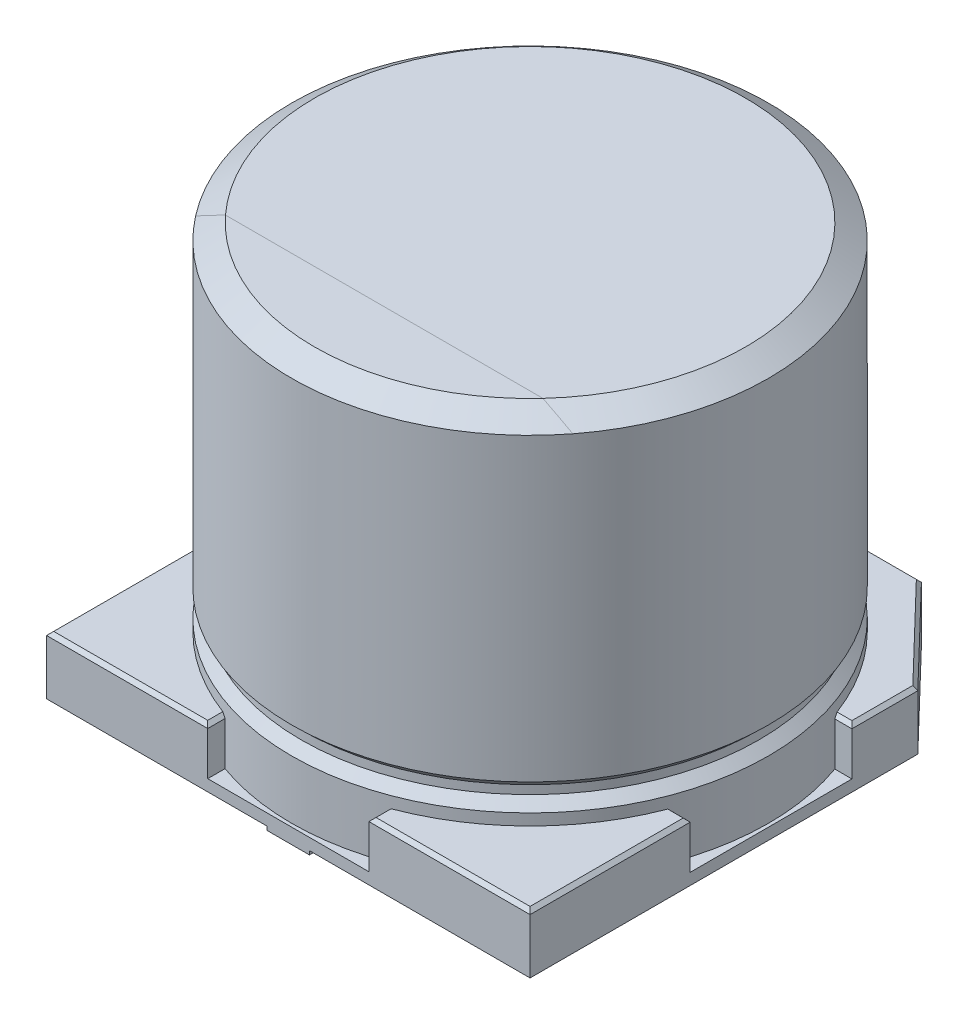
SolidWorks part; units mm, degrees
ref_plane "Front Plane" through (0, 0, 0) normal (0, 0, 1) x (1, 0, 0)
ref_plane "Top Plane" through (0, 0, 0) normal (0, 1, 0) x (1, 0, 0)
ref_plane "Right Plane" through (0, 0, 0) normal (1, 0, 0) x (0, 0, -1)
sketch "Sketch1" plane through (0, 0, 0) normal (0, 1, 0) x (1, 0, 0)
  line L0 (0, 3.315) -> (0, -3.315) construction
  point P2 (0, 0)
  line B0 (3.315, -3.315) -> (3.315, 2.0024)
  line B1 (0.2896, -3.315) -> (3.315, -3.315)
  line B2 (2.0517, 3.315) -> (3.315, 2.0024)
  line B3 (2.0517, 3.315) -> (0.2875, 3.315)
  line B4 (0.2882, 1.5924) -> (0.2875, 3.315)
  line B5 (0.2875, 3.315) -> (-0.2875, 3.315)
  line B6 (-0.2875, 3.315) -> (-0.2882, 1.5924)
  line B7 (-0.2875, 3.315) -> (-2.0519, 3.315)
  line B8 (-0.2882, 1.5924) -> (0.2882, 1.5924)
  line B9 (0.2889, -1.5924) -> (-0.2889, -1.5924)
  line B10 (0.2896, -3.315) -> (0.2889, -1.5924)
  line B11 (-0.2889, -1.5924) -> (-0.2896, -3.315)
  line B12 (-0.2896, -3.315) -> (0.2896, -3.315)
  line B13 (-3.315, -3.315) -> (-0.2896, -3.315)
  line B14 (-3.315, 2.0024) -> (-3.315, -3.315)
  line B15 (-3.315, 2.0024) -> (-2.0519, 3.315)
  line B16 (-3.315, -1.1187) -> (-1.11, -1.105)
  line B17 (-1.11, -1.105) -> (-1.105, -3.315)
  line B18 (-1.115, 1.105) -> (-3.315, 1.0983)
  line B19 (-1.12, 3.315) -> (-1.115, 1.105)
  line B20 (1.11, -1.105) -> (3.315, -1.1187)
  line B21 (1.105, -3.315) -> (1.11, -1.105)
  line B22 (1.115, 1.105) -> (1.12, 3.315)
  line B23 (3.315, 1.0983) -> (1.115, 1.105)
sketch_block_instance "Block1-1"
sketch_block "Block1"
extrude "Boss-Extrude1" add sketch "Sketch1" against normal blind 0.1571 contours B19 B7 B15 B14 B18 | L0 B8 B6 B7 B19 B18 B14 B16 B17 B13 B11 B9 | B17 B16 B14 B13 | B9 L0 B12 B10 | L0 B9 B11 B12 | L0 B5 B6 B8 | B5 L0 B8 B4 | B8 L0 B9 B10 B1 B21 B20 B0 B23 B22 B3 B4 | B23 B0 B2 B3 B22 | B21 B1 B0 B20 region at (0.1439, 0, -2.4533) region at (-0.1439, 0, -2.4533) region at (1.3107, 0, -0.0031) region at (-1.3107, 0, -0.0031) region at (0.1446, 0, 2.454) region at (-0.1446, 0, 2.454) region at (2.0777, 0, -2.0703) region at (-2.0777, 0, -2.0704) region at (-2.2101, 0, 2.2138) region at (2.2101, 0, 2.2138)
extrude "Boss-Extrude2" add sketch "Sketch1<4>" along normal blind 0.6443 contours B19 B7 B15 B14 B18 | B17 B16 B14 B13 | B23 B0 B2 B3 B22 | B21 B1 B0 B20 region at (2.2101, 0, 2.2138) region at (2.0777, 0, -2.0703) region at (-2.2101, 0, 2.2138) region at (-2.0777, 0, -2.0704)
sketch "Sketch1<4>" plane through (0, 0, 0) normal (0, 1, 0) x (1, 0, 0) same geometry as "Sketch1"
chamfer "Chamfer1" distance 0.0487 angle 45 18 edges at (2.2125, 0.6443, 1.1119) (3.315, 0.6443, 2.2169) (2.21, 0.6443, 3.315) (1.1075, 0.6443, 2.21) (1.1175, 0.6443, -2.21) (1.5858, 0.6443, -3.315) (2.6833, 0.6443, -2.6587) (3.315, 0.6443, -1.5504) (2.215, 0.6443, -1.1017) (-2.215, 0.6443, -1.1017) (-3.315, 0.6443, -1.5504) (-2.6835, 0.6443, -2.6587) (-1.586, 0.6443, -3.315) (-1.1175, 0.6443, -2.21) (-2.21, 0.6443, 3.315) (-3.315, 0.6443, 2.2169) (-2.2125, 0.6443, 1.1119) (-1.1075, 0.6443, 2.21)
extrude "Boss-Extrude3" add sketch "Sketch1<5>" against normal blind 0.0514 from surface contours L0 B9 B11 B12 | B9 L0 B12 B10 | L0 B5 B6 B8 | B5 L0 B8 B4 region at (0.1439, 0, -2.4533) region at (-0.1439, 0, -2.4533) region at (0.1446, 0, 2.454) region at (-0.1446, 0, 2.454) starting at face at (0, -0.1571, -0.6675)
sketch "Sketch1<5>" plane through (0, 0, 0) normal (0, 1, 0) x (1, 0, 0) same geometry as "Sketch1"
sketch "Sketch2" plane through (0, 0, 0) normal (0, 1, 0) x (1, 0, 0)
  circle A0 centre (0, 0) radius 3.27
  dimension "D1" = 6.54
extrude "Boss-Extrude4" add sketch "Sketch2" along normal blind 5.5
chamfer "Chamfer2" distance 0.2155 distance2 0.314 1 edges at (0, 5.5, 3.27) first distance on face at (0, 0.4133, 0.0057)
ref_axis "Axis1" through (0, 5.2845, 0) along (0, -1, 0)
sketch "Sketch3" plane through (0, 0, 0) normal (0, 0, 1) x (1, 0, 0)
  line L0 (3.1392, 1.0429) -> (3.1392, 0.9251)
  line L1 (3.27, 0) -> (3.27, 5.2845) construction
  line L2 (3.27, 1.168) -> (3.1392, 1.0429)
  line L3 (3.27, 1.168) -> (3.27, 0.8)
  line L4 (3.27, 0.984) -> (0, 0.984) construction
  line L5 (0, 5.2845) -> (0, 0) construction
  line L6 (3.27, 0.8) -> (3.1392, 0.9251)
  line L7 (1.1055, 0) -> (-1.1055, 0) construction
  point P10 (3.1392, 0.984)
  dimension "D1" = 0.368
  dimension "D2" = 0.1308
  dimension "D3" = 0.1251
  dimension "D4" = 0.8
revolve "Cut-Revolve1" cut sketch "Sketch3" angle 360 about axis through (0, 5.2845, 0) along (0, -1, 0)
sketch "Sketch4" plane through (0, 5.5, 0) normal (0, 1, 0) x (1, 0, 0)
  line L0 (-2.5871, -2) -> (2.5871, -2)
  arc A0 (-3.0551, -1.1658) -> (-1.1543, -3.0595) centre (0, 0) ccw construction
  arc A1 (1.1543, -3.0595) -> (3.0551, -1.1658) centre (0, 0) ccw construction
  dimension "D1" = 2
split line "Split Line1"
sketch "Sketch5" plane through (0, -0.1571, 0) normal (0, -1, 0) x (1, 0, 0)
  circle A0 centre (0, 0) radius 1 construction
  dimension "D1" = 2
